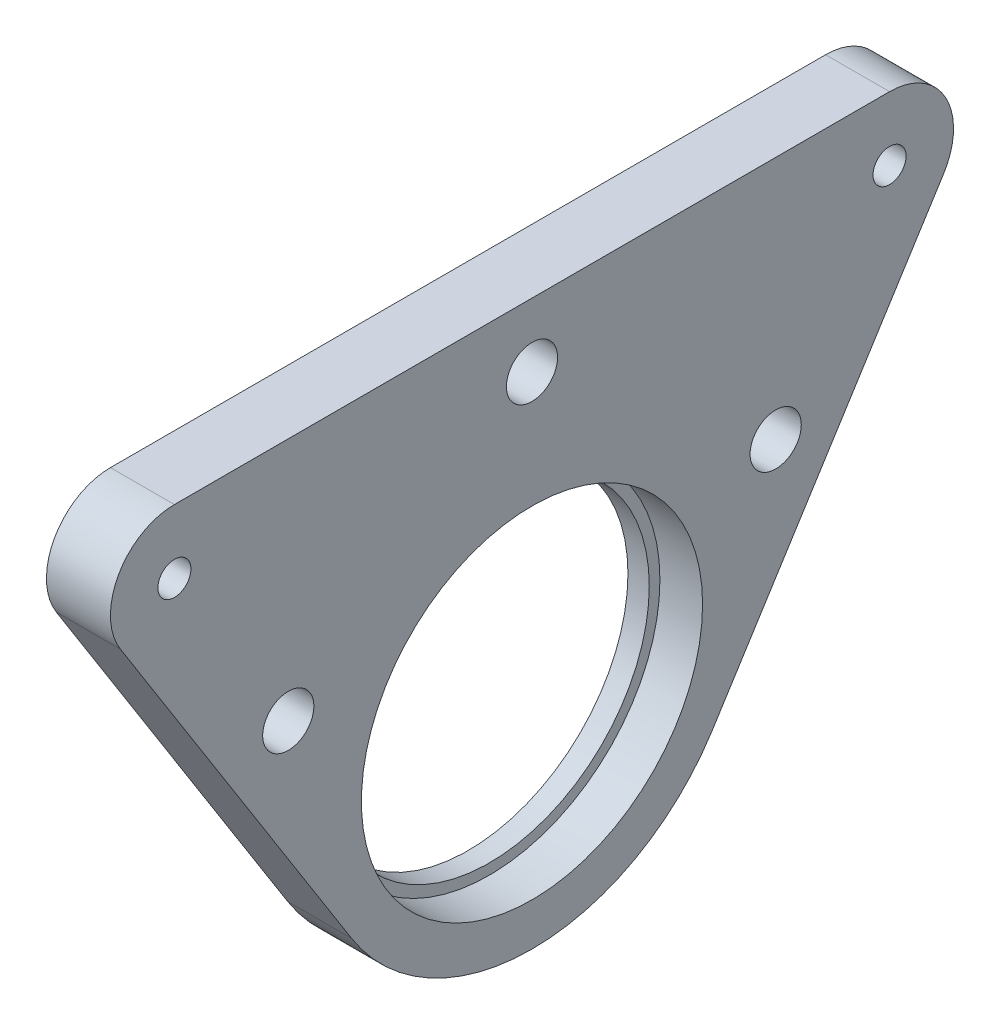
SolidWorks part; units mm, degrees
ref_plane "Front Plane" through (0, 0, 0) normal (0, 0, 1) x (1, 0, 0)
ref_plane "Top Plane" through (0, 0, 0) normal (0, 1, 0) x (1, 0, 0)
ref_plane "Right Plane" through (0, 0, 0) normal (1, 0, 0) x (0, 0, -1)
sketch "Sketch1" plane through (0, 0, 0) normal (1, 0, 0) x (0, 0, -1)
  circle A0 centre (0, 0) radius 15
  circle A1 centre (0, 0) radius 20
  dimension "D1" = 30
  dimension "D2" = 40
extrude "Boss-Extrude1" add sketch "Sketch1" along normal blind 2
sketch "Sketch2" plane through (2, 0, 0) normal (1, 0, 0) x (0, 0, -1)
  circle A0 centre (0, 0) radius 16
  circle A1 centre (0, 0) radius 20 construction
  circle A2 centre (0, 0) radius 20
  dimension "D1" = 32
extrude "Boss-Extrude2" add sketch "Sketch2" along normal blind 4
sketch "Sketch3" plane through (6, 0, 0) normal (1, 0, 0) x (0, 0, -1)
  line L0 (-33.5359, 26.8817) -> (0, 0) construction
  line L1 (0, 0) -> (33.5359, 26.8817) construction
  line L2 (-38.6088, 23.6778) -> (-16.9099, -10.6797)
  line L3 (-33.5359, 32.8817) -> (33.5359, 32.8817)
  line L4 (16.9099, -10.6797) -> (38.6088, 23.6778)
  circle A0 centre (-33.5359, 26.8817) radius 2
  circle A1 centre (33.5359, 26.8817) radius 2
  arc A2 (-33.5359, 32.8817) -> (-38.6088, 23.6778) centre (-33.5359, 26.8817) ccw
  arc A3 (38.6088, 23.6778) -> (33.5359, 32.8817) centre (33.5359, 26.8817) ccw
  circle A4 centre (0, 0) radius 20 construction
  arc A5 (16.9099, -10.6797) -> (-16.9099, -10.6797) centre (0, 0) ccw
  circle A6 centre (-33.5359, 26.8817) radius 6 construction
  circle A7 centre (33.5359, 26.8817) radius 6 construction
  dimension "D1" = 4
  dimension "D2" = 102.57
  dimension "D3" = 42.98
  dimension "D4" = 4
extrude "Boss-Extrude3" add sketch "Sketch3" against normal up to surface (6 mm away) up to face at (0, 0, -20)
sketch "Sketch4" plane through (6, 0, 0) normal (1, 0, 0) x (0, 0, -1)
  line L0 (-33.5359, 26.8817) -> (-22.8562, 9.9718) construction
  line L1 (-38.6088, 23.6778) -> (-16.9099, -10.6797) construction
  line L2 (0, 0) -> (0, 15) construction
  line L3 (33.5359, 26.8817) -> (22.8562, 9.9718) construction
  circle A0 centre (-22.8562, 9.9718) radius 2.4
  circle A2 centre (0, 0) radius 15 construction
  circle A3 centre (22.8562, 9.9718) radius 2.4
  circle A4 centre (0, 26.8817) radius 2.4
  dimension "D1" = 4.8
  dimension "D2" = 20
extrude "Cut-Extrude1" cut sketch "Sketch4" against normal up to surface (6 mm away) up to face at (0, 14.2393, 0)
sketch "Sketch5" plane through (0, 0, 0) normal (1, 0, 0) x (0, 0, -1)
  circle A0 centre (33.5359, 26.8817) radius 2 construction
  circle A1 centre (-33.5359, 26.8817) radius 2 construction
  circle A2 centre (33.5359, 26.8817) radius 2
  circle A3 centre (-33.5359, 26.8817) radius 2
  circle A4 centre (-33.5359, 26.8817) radius 1.55
  circle A5 centre (33.5359, 26.8817) radius 1.55
  dimension "D1" = 3.1
extrude "Boss-Extrude4" add sketch "Sketch5" along normal up to surface (6 mm away) up to face at (6, 9.9718, 20.4562)
